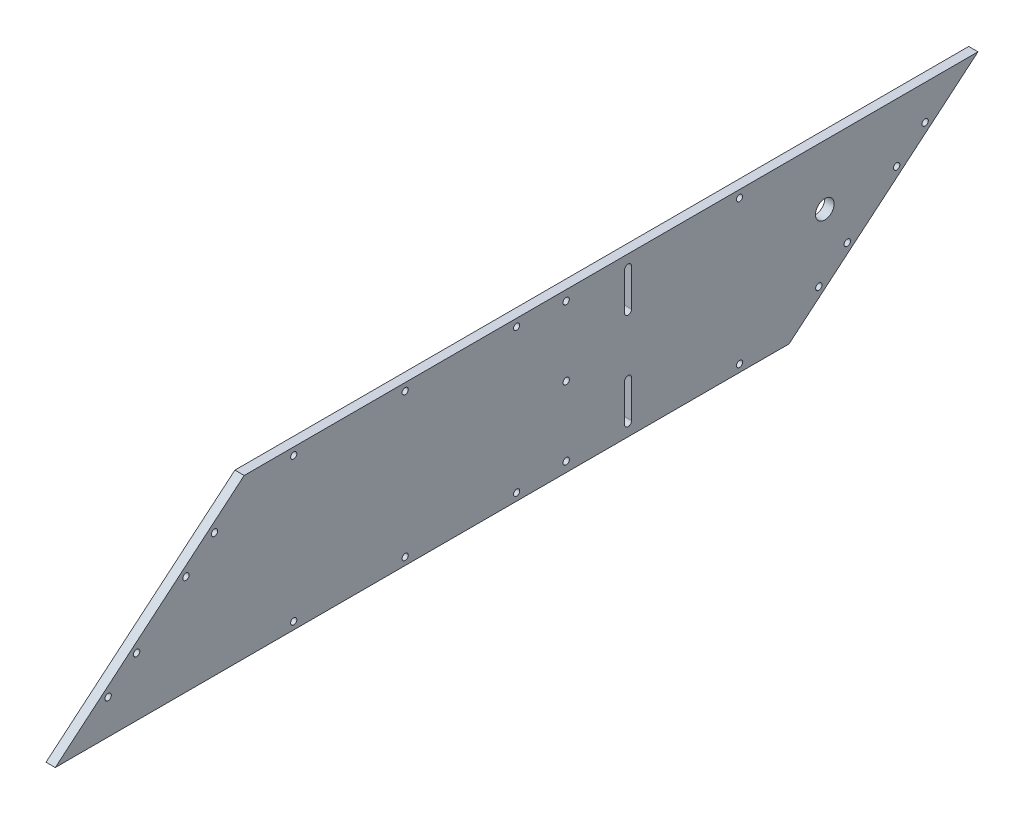
SolidWorks part; units mm, degrees
material "6061-T6 (SS)"
ref_plane "Front Plane" through (0, 0, 0) normal (0, 0, 1) x (1, 0, 0)
ref_plane "Top Plane" through (0, 0, 0) normal (0, 1, 0) x (1, 0, 0)
ref_plane "Right Plane" through (0, 0, 0) normal (1, 0, 0) x (0, 0, -1)
sketch "Sketch1" plane through (0, 0, 0) normal (1, 0, 0) x (0, 0, -1)
  line L0 (0, 12.7) -> (0, -12.7) construction
  line L1 (0, -12.7) -> (33.2976, -40.64) construction
  line L2 (33.2976, -40.64) -> (312.6976, -40.64)
  line L3 (312.6976, -40.64) -> (345.9952, -12.7)
  line L4 (345.9952, -12.7) -> (345.9952, 12.7) construction
  line L5 (345.9952, 12.7) -> (312.6976, 40.64) construction
  line L6 (312.6976, 40.64) -> (33.2976, 40.64)
  line L7 (33.2976, 40.64) -> (0, 12.7)
  line L8 (33.2976, 40.64) -> (33.2976, -40.64) construction
  line L9 (312.6976, 40.64) -> (312.6976, -40.64) construction
  line L10 (0, 0) -> (345.9952, 0) construction
  line L11 (0, 12.7) -> (-63.5681, -40.64)
  line L12 (-63.5681, -40.64) -> (33.2976, -40.64)
  line L13 (312.6976, 40.64) -> (409.5633, 40.64)
  line L14 (409.5633, 40.64) -> (345.9952, -12.7)
  point P10 (33.2976, 0)
  point P12 (312.6976, 0)
  dimension "D1" = 81.28
  dimension "D2" = 279.4
  dimension "D3" = 25.4
  dimension "D4" = 40
extrude "Boss-Extrude1" add sketch "Sketch1" along normal blind 4.7625
sketch "Sketch2" plane through (4.7625, 0, 0) normal (1, 0, 0) x (0, 0, -1)
  line L0 (-3.2177, 10) -> (373.048, 10) construction
  line L1 (312.6976, -40.64) -> (409.5633, 40.64) construction
  line L2 (345.048, 10) -> (245.048, 10) construction
  line L3 (245.048, -5) -> (345.048, -5) construction
  line L4 (245.048, -5) -> (245.048, 25) construction
  line L5 (245.048, 25) -> (345.048, 25) construction
  line L6 (345.048, -5) -> (345.048, 25) construction
  line L7 (33.2976, 40.64) -> (-63.5681, -40.64) construction
  line L9 (0, 0) -> (361.1305, 0) construction
  circle A0 centre (300.048, 10) radius 6.9977 construction
  circle A1 centre (282.2147, 8) radius 1.4986 construction
  circle A2 centre (270.2178, 15.9334) radius 0.9906 construction
  circle A3 centre (282.2147, 8) radius 11.4777 construction
  circle A4 centre (270.2178, 15.9334) radius 7.1501 construction
  circle A5 centre (300.048, 10) radius 12.827 construction
  circle A6 centre (261.048, 10) radius 14 construction
  circle A7 centre (282.2147, 8) radius 5.1181 construction
  circle A8 centre (331.0042, 10) radius 4.7625
  point P11 (300.048, 10)
  point P12 (282.2147, 8)
  point P13 (270.2178, 15.9334)
  point P23 (261.048, 10)
  dimension "D5" = 13.9954
  dimension "D6" = 2.9972
  dimension "D7" = 1.9812
  dimension "D8" = 25.654
  dimension "D9" = 22.9553
  dimension "D10" = 14.3002
  dimension "D12" = 28
  dimension "D13" = 10.2362
  dimension "D17" = 9.525
  dimension "D1" = 17.9451
  dimension "D2" = 14.3828
  dimension "D3" = 30
  dimension "D4" = 100
  dimension "D11" = 10.922
  dimension "D14" = 16
  dimension "D15" = 13
  dimension "D16" = 55
  dimension "D18" = 30.9562
  dimension "D19" = 28
  dimension "D20" = 10
extrude "Gearbox (with Press fits)" cut sketch "Sketch2" against normal through all
sketch "Sketch3" plane through (4.7625, 0, 0) normal (1, 0, 0) x (0, 0, -1)
  line L0 (0, 0) -> (361.1305, 0) construction
  line L1 (28.757, 36.83) -> (405.0227, 36.83) construction
  line L2 (230.1476, 36.83) -> (230.1476, -36.83) construction
  line L3 (230.1476, 34.29) -> (230.1476, 15.24) construction
  line L4 (33.2976, 40.64) -> (-63.5681, -40.64) construction
  line L5 (409.5633, 40.64) -> (33.2976, 40.64) construction
  line L6 (312.6976, -40.64) -> (409.5633, 40.64) construction
  line L7 (231.9764, 34.29) -> (231.9764, 15.24)
  line L8 (228.3188, 34.29) -> (228.3188, 15.24)
  line L9 (409.5633, 40.64) -> (33.2976, 40.64) construction
  line L10 (230.1476, -34.29) -> (230.1476, -15.24) construction
  line L11 (231.9764, -34.29) -> (231.9764, -15.24)
  line L12 (228.3188, -34.29) -> (228.3188, -15.24)
  circle A0 centre (287.2976, 36.83) radius 1.5811
  circle A1 centre (230.1476, 36.83) radius 1.5811 construction
  circle A2 centre (172.9976, 36.83) radius 1.5811
  circle A3 centre (115.8476, 36.83) radius 1.5811
  circle A4 centre (58.6976, 36.83) radius 1.5812
  circle A5 centre (58.6976, -36.83) radius 1.5812
  circle A6 centre (115.8476, -36.83) radius 1.5811
  circle A7 centre (172.9976, -36.83) radius 1.5811
  circle A8 centre (230.1476, -36.83) radius 1.5811 construction
  circle A9 centre (287.2976, -36.83) radius 1.5811
  arc A10 (231.9764, 34.29) -> (228.3188, 34.29) centre (230.1476, 34.29) ccw
  arc A11 (228.3188, 15.24) -> (231.9764, 15.24) centre (230.1476, 15.24) ccw
  arc A12 (231.9764, -34.29) -> (228.3188, -34.29) centre (230.1476, -34.29) cw
  arc A13 (228.3188, -15.24) -> (231.9764, -15.24) centre (230.1476, -15.24) cw
  point P32 (230.1476, 24.765)
  point P43 (230.1476, -24.765)
  dimension "D1" = 3.1623
  dimension "D2" = 25.4
  dimension "D4" = 3.81
  dimension "D5" = 3.6576
  dimension "D6" = 6.35
  dimension "D7" = 19.05
  dimension "D3" = 5
extrude "Cut-Extrude1" cut sketch "Sketch3" against normal through all
hole_wizard "#4 Clearance Hole2" positions "Sketch5" profile "Sketch4" hole size "#4" standard "ANSI Inch"
sketch "Sketch5" plane through (4.7625, 0, 0) normal (1, 0, 0) x (0, 0, -1)
  line L12 (-15.1353, 0) -> (361.1305, 0) construction
  line L13 (33.2976, 40.64) -> (-63.5681, -40.64) construction
  line L14 (312.6976, -40.64) -> (409.5633, 40.64) construction
  line L17 (403.636, 40.64) -> (306.7703, -40.64) construction
  line L18 (409.5633, 40.64) -> (33.2976, 40.64) construction
  line L19 (-63.5681, -40.64) -> (312.6976, -40.64) construction
  line L21 (39.2249, 40.64) -> (-57.6408, -40.64) construction
  line L23 (382.4437, 22.8575) -> (18.0326, 22.8575) construction
  line L25 (367.8505, 10.6124) -> (3.4394, 10.6124) construction
  line L27 (342.5558, -10.6124) -> (-21.8554, -10.6124) construction
  line L29 (327.9626, -22.8575) -> (-36.4485, -22.8575) construction
  line L31 (355.2032, 0) -> (0, 0) construction
  point P60 (327.9626, -22.8575)
  point P62 (342.5558, -10.6124)
  point P64 (367.8505, 10.6124)
  point P66 (382.4437, 22.8575)
  point P75 (18.0326, 22.8575)
  point P79 (3.4394, 10.6124)
  point P83 (-21.8554, -10.6124)
  point P87 (-36.4485, -22.8575)
  dimension "D1" = 19.05
  dimension "D2" = 19.05
  dimension "D3" = 16.51
  dimension "D4" = 16.51
  dimension "D5" = 3.81
  dimension "D6" = 3.81
sketch "Sketch4" plane through (4.7625, -22.8575, -327.9626) normal (0, 1, 0) x (0, 0, -1)
  line L0 (0, 0) -> (0, 29.6826)
  line L1 (0, 29.6826) -> (1.6319, 28.702)
  line L2 (1.6319, 28.702) -> (1.6319, 0)
  line L5 (1.6319, 0) -> (0, 0)
  line L10 (0, 29.6826) -> (-1.632, 28.702) construction
  line L11 (0, -6.35) -> (0, 107.95) construction
  dimension "Hole Dia." = 3.2639
  dimension "Hole Depth" = 28.702
  dimension "Drill Angle" = 118
hole_wizard "#4 Clearance Hole1" positions "Sketch10" profile "Sketch8" hole size "#4" standard "ANSI Inch"
sketch "Sketch10" plane through (4.7625, 0, 0) normal (1, 0, 0) x (0, 0, -1)
  line L0 (27.2435, 35.56) -> (403.5092, 35.56) construction
  line L1 (33.2976, 40.64) -> (-63.5681, -40.64) construction
  line L3 (312.6976, -40.64) -> (409.5633, 40.64) construction
  line L4 (-15.1353, 0) -> (361.1305, 0) construction
  line L6 (409.5633, 40.64) -> (33.2976, 40.64) construction
  line L7 (198.3976, 35.56) -> (198.3976, -35.56) construction
  point P16 (198.3976, 35.56)
  point P19 (198.3976, -35.56)
  point P24 (198.3976, 0)
  dimension "D1" = 5.08
  dimension "D2" = 165.1
sketch "Sketch8" plane through (4.7625, 35.56, -198.3976) normal (0, 1, 0) x (0, 0, -1)
  line L0 (0, 0) -> (0, 5.8066)
  line L1 (0, 5.8066) -> (1.6319, 4.826)
  line L2 (1.6319, 4.826) -> (1.6319, 0)
  line L5 (1.6319, 0) -> (0, 0)
  line L10 (0, 5.8066) -> (-1.6319, 4.826) construction
  line L11 (0, -6.35) -> (0, 107.95) construction
  dimension "Hole Dia." = 3.2639
  dimension "Hole Depth" = 4.826
  dimension "Drill Angle" = 118
sketch "Sketch11" plane through (4.7625, 0, 0) normal (1, 0, 0) x (0, 0, -1)
  line L0 (18.1623, 27.94) -> (394.4281, 27.94) construction
  line L1 (33.2976, 40.64) -> (-63.5681, -40.64) construction
  line L2 (312.6976, -40.64) -> (409.5633, 40.64) construction
  line L3 (-48.4329, -27.94) -> (327.8329, -27.94) construction
  line L4 (-21.9928, -22.3328) -> (35.7449, 26.1148)
  line L5 (39.9758, 25.9814) -> (90.8271, -22.4663)
  line L6 (88.637, -27.94) -> (-19.9519, -27.94)
  line L7 (62.0768, 22.4663) -> (112.7937, -25.8534)
  line L8 (117.1739, -25.8534) -> (167.8909, 22.4663)
  line L9 (165.7008, 27.94) -> (64.2668, 27.94)
  line L10 (186.6825, 22.8285) -> (139.1405, -22.4663)
  line L11 (141.3306, -27.94) -> (188.8726, -27.94)
  line L12 (192.0476, -24.765) -> (192.0476, 20.5298)
  line L13 (204.7476, 18.9322) -> (204.7476, -24.765)
  line L14 (409.5633, 40.64) -> (33.2976, 40.64) construction
  line L15 (-63.5681, -40.64) -> (312.6976, -40.64) construction
  line L16 (207.9226, -27.94) -> (243.0966, -27.94)
  line L17 (245.5699, -22.7741) -> (210.3959, 20.9231)
  line L18 (225.2091, 22.7741) -> (263.9995, -25.4158)
  line L19 (268.5136, -25.8571) -> (325.9442, 22.3328)
  line L20 (323.9033, 27.94) -> (227.6824, 27.94)
  line L21 (114.9838, 27.94) -> (114.9838, -27.94) construction
  circle A0 centre (198.3976, 0) radius 6.35 construction
  arc A1 (188.8726, -27.94) -> (192.0476, -24.765) centre (188.8726, -24.765) ccw
  arc A2 (139.1405, -22.4663) -> (141.3306, -27.94) centre (141.3306, -24.765) ccw
  arc A3 (192.0476, 20.5298) -> (186.6825, 22.8285) centre (188.8726, 20.5298) ccw
  arc A4 (167.8909, 22.4663) -> (165.7008, 27.94) centre (165.7008, 24.765) ccw
  arc A5 (62.0768, 22.4663) -> (64.2668, 27.94) centre (64.2668, 24.765) cw
  arc A6 (112.7937, -25.8534) -> (117.1739, -25.8534) centre (114.9838, -23.5547) ccw
  arc A7 (90.8271, -22.4663) -> (88.637, -27.94) centre (88.637, -24.765) cw
  arc A8 (35.7449, 26.1148) -> (39.9758, 25.9814) centre (37.7857, 23.6826) cw
  arc A9 (-21.9928, -22.3328) -> (-19.9519, -27.94) centre (-19.9519, -24.765) ccw
  circle A10 centre (331.0042, 10) radius 12.7 construction
  arc A11 (325.9442, 22.3328) -> (323.9033, 27.94) centre (323.9033, 24.765) ccw
  arc A12 (225.2091, 22.7741) -> (227.6824, 27.94) centre (227.6824, 24.765) cw
  arc A13 (263.9995, -25.4158) -> (268.5136, -25.8571) centre (266.4728, -23.4249) ccw
  arc A14 (243.0966, -27.94) -> (245.5699, -22.7741) centre (243.0966, -24.765) ccw
  arc A15 (204.7476, -24.765) -> (207.9226, -27.94) centre (207.9226, -24.765) ccw
  arc A16 (204.7476, 18.9322) -> (210.3959, 20.9231) centre (207.9226, 18.9322) cw
  point P26 (192.0476, -27.94)
  point P29 (133.3952, -27.94)
  point P32 (192.0476, 27.94)
  point P35 (173.6362, 27.94)
  point P38 (56.3315, 27.94)
  point P41 (114.9838, -27.94)
  point P44 (96.5724, -27.94)
  point P47 (37.92, 27.94)
  point P50 (-28.6752, -27.94)
  point P62 (332.6266, 27.94)
  point P65 (221.0509, 27.94)
  point P68 (266.0314, -27.94)
  point P71 (249.7281, -27.94)
  point P74 (204.7476, -27.94)
  point P77 (204.7476, 27.94)
  dimension "D3" = 12.7
  dimension "D7" = 3.175
  dimension "D9" = 25.4
  dimension "D10" = 3.175
  dimension "D1" = 12.7
  dimension "D2" = 12.7
  dimension "D4" = 12.7
  dimension "D5" = 12.7
  dimension "D6" = 12.7
  dimension "D8" = 12.7
extrude "Cut-Extrude2" [suppressed] cut sketch "Sketch11" against normal through all
